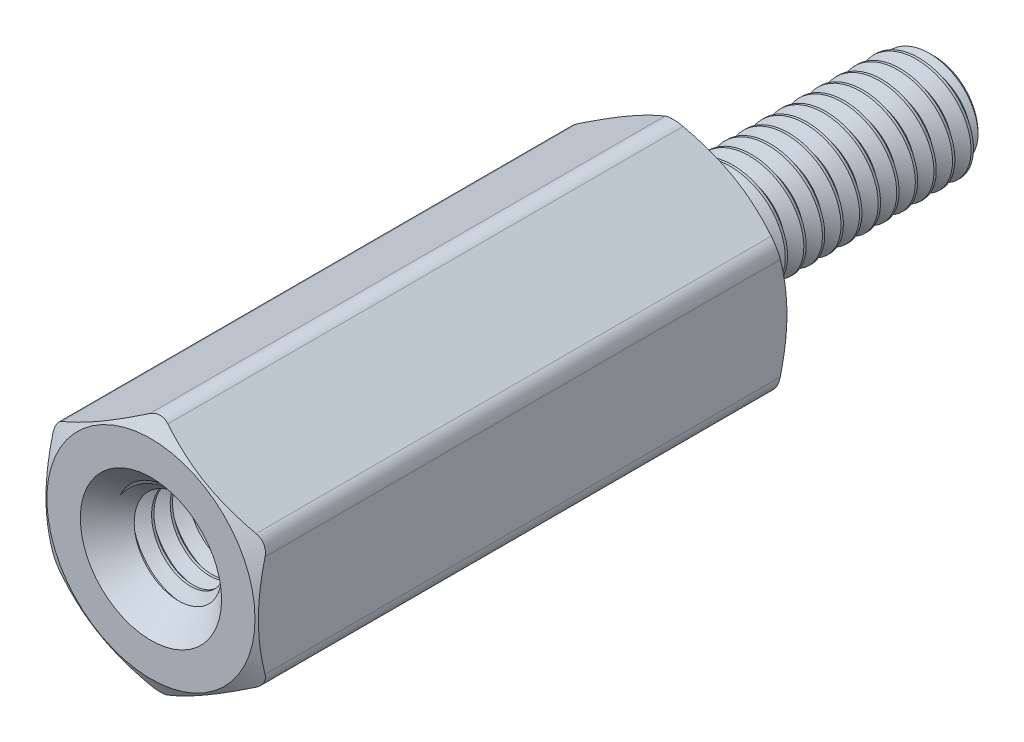
SolidWorks part; units mm, degrees
ref_plane "Front Plane" through (0, 0, 0) normal (0, 0, 1) x (1, 0, 0)
ref_plane "Top Plane" through (0, 0, 0) normal (0, 1, 0) x (1, 0, 0)
ref_plane "Right Plane" through (0, 0, 0) normal (1, 0, 0) x (0, 0, -1)
sketch "Sketch1" plane through (0, 0, 0) normal (0, 0, 1) x (1, 0, 0)
  line L1 (4, 2.3094) -> (0, 4.6188)
  line L2 (0, 4.6188) -> (-4, 2.3094)
  line L3 (-4, 2.3094) -> (-4, -2.3094)
  line L4 (-4, -2.3094) -> (0, -4.6188)
  line L5 (0, -4.6188) -> (4, -2.3094)
  line L6 (4, -2.3094) -> (4, 2.3094)
  circle A0 centre (0, 0) radius 4 construction
  point P10 (0, -4)
  dimension "Hex Size" = 8
sketch "Sketch2" plane through (0, 0, 0) normal (1, 0, 0) x (0, 0, -1)
  line L0 (9.5, 0) -> (-20, 0) construction
  line L2 (0, 2) -> (0, -2) construction
  line L3 (-8.9, 2) -> (-8.9, -2) construction
  line L4 (-20.6563, 2.0758) -> (-20.3063, 1.4696) construction
  line L5 (-20.3063, 1.4696) -> (-19.9563, 2.0758) construction
  line L6 (-19.9563, 2.0758) -> (-20.6563, 2.0758) construction
  line L7 (-20.6125, 2) -> (-20, 2) construction
  line L8 (-20.35, 1.5453) -> (-20.2625, 1.5453) construction
  line L9 (-20.3063, 1.5453) -> (-20.3063, 1.4696) construction
  line L10 (-20.3063, 2) -> (-20.3063, 2.0758) construction
  line L11 (9.4562, 2.0758) -> (10.1562, 2.0758) construction
  line L12 (10.1562, 2.0758) -> (9.8062, 1.4696) construction
  line L13 (9.8062, 1.4696) -> (9.4562, 2.0758) construction
  line L14 (9.5, 2) -> (10.1125, 2) construction
  line L15 (9.7625, 1.5453) -> (9.85, 1.5453) construction
  line L16 (9.8062, 1.5453) -> (9.8062, 1.4696) construction
  line L17 (9.8062, 2) -> (9.8062, 2.0758) construction
  line L18 (0, 4.6188) -> (-20, 4.6188) construction
  point P6 (0, 0)
  point P9 (-8.9, 0)
  dimension "Length" = 20
sketch "Sketch3" plane through (0, 0, 0) normal (1, 0, 0) x (0, 0, -1)
  line L0 (-8.9, 0) -> (9.5, 0)
  line L1 (-8.9, 2) -> (-8.9, -2) construction
  line L2 (9.5, 0) -> (9.5, 1.65)
  line L3 (9.5, 1.65) -> (9.15, 2)
  line L4 (9.15, 2) -> (1.4025, 2)
  line L5 (1.4025, 2) -> (1.14, 1.5453)
  line L6 (-8.9, 0) -> (-8.9, 1.65)
  line L7 (-8.9, 1.65) -> (-9.25, 2)
  line L8 (-9.25, 2) -> (-19.65, 2)
  line L9 (-19.65, 2) -> (-20, 2.35)
  line L10 (9.15, 0) -> (9.15, -2) construction
  line L11 (-20, 2.35) -> (-20, 4)
  line L12 (-20, 4) -> (0, 4)
  line L14 (1.14, 1.5453) -> (0.35, 1.5453)
  line L15 (0, 1.8953) -> (0, 4)
  arc A0 (0, 1.8953) -> (0.35, 1.5453) centre (0.35, 1.8953) ccw
  point P5 (-20, -4)
  point P8 (-18.25, -2)
  point P9 (7.75, -2)
  point P27 (0, 1.5453)
  dimension "D4" = 0.35
  dimension "D2" = 0.35
  dimension "D1" = 45
  dimension "D6" = 1.75
  dimension "D7" = 60
  dimension "D3" = 1.75
  dimension "D5" = 1.14
revolve "Revolve1" add sketch "Sketch3" angle 360 about L0
sketch "Sketch4" plane through (0, 0, 20) normal (0, 0, 1) x (1, 0, 0)
  line L0 (0, 4) -> (0, 2) construction
  line L1 (-4, 2.3094) -> (-4, -2.3094)
  line L2 (-4, -2.3094) -> (0, -4.6188)
  line L3 (0, -4.6188) -> (4, -2.3094)
  line L4 (4, -2.3094) -> (4, 2.3094)
  line L5 (4, 2.3094) -> (0, 4.6188)
  line L6 (0, 4.6188) -> (-4, 2.3094)
  circle A0 centre (0, 0) radius 4 construction
  circle A1 centre (0, 0) radius 3
  circle A2 centre (0, 0) radius 4 construction
  point P16 (0, 3)
extrude "Boss-Extrude1" add sketch "Sketch4" against normal up to surface (20 mm away) up to face at (0, 4, 0)
sketch "Sketch5" plane through (0, 0, 20) normal (0, 0, 1) x (1, 0, 0)
  line L0 (-1.1472, 1.6383) -> (1.1472, -1.6383) construction
  line L1 (0, 2) -> (0, -2) construction
  line L3 (0, -2.7928) -> (0, 2.7928) construction
  circle A0 centre (0, 0) radius 3.92
  point P11 (1.1472, -1.6383)
  dimension "D1" = 7.84
  dimension "D2" = 35
extrude "Cut-Extrude1" cut sketch "Sketch5" against normal through all draft 60 flip side to cut
sketch "Sketch6" plane through (0, 0, 0) normal (0, 0, -1) x (-1, 0, 0)
  circle A0 centre (0, 0) radius 3.92
  circle A1 centre (0, 0) radius 3.92 construction
extrude "Cut-Extrude2" cut sketch "Sketch6" against normal through all draft 60 flip side to cut
fillet "Fillet1" radius 0.68 6 edges at (0, 4.6188, 10) (-4, -2.3094, 10) (0, -4.6188, 10) (4, -2.3094, 10) (4, 2.3094, 10) (-4, 2.3094, 10)
sketch "Drawing1" plane through (0, 0, 0) normal (1, 0, 0) x (0, 0, -1)
  line L0 (-20, 2) -> (-8.9, 2) construction
  line L1 (-8.9, 2) -> (-8.9, -2) construction
  line L2 (-8.9, -2) -> (-20, -2) construction
sketch "Sketch7" plane through (0, 0, 0) normal (-1, 0, 0) x (0, 0, 1)
  line L0 (-9.7625, 1.5453) -> (-9.85, 1.5453)
  line L1 (-9.85, 1.5453) -> (-10.1344, 2.0379)
  line L2 (-10.1562, 2.0758) -> (-9.8062, 1.4696) construction
  line L3 (-10.1344, 2.0379) -> (-9.4781, 2.0379)
  line L4 (-9.8062, 1.4696) -> (-9.4562, 2.0758) construction
  line L5 (-9.4781, 2.0379) -> (-9.7625, 1.5453)
  line L6 (-9.8062, 2) -> (-9.8062, 2.0758) construction
  point P12 (-9.8062, 2.0379)
sketch "Sketch8" plane through (0, 0, -9.5) normal (0, 0, -1) x (-1, 0, 0)
  circle A0 centre (0, 0) radius 2
curve "Helix/Spiral1" pitch 0.7 height 9.215 turns 13.1643
sweep "Cut-Sweep1" cut profiles "Sketch7" path "Helix/Spiral1" align with end faces yes
sketch "Sketch9" plane through (0, 0, 8.9) normal (0, 0, 1) x (1, 0, 0)
  circle A0 centre (0, 0) radius 2.35
extrude "Boss-Extrude2" add sketch "Sketch9" along normal up to surface (11.1 mm away)
sketch "Sketch10" plane through (0, 0, 0) normal (1, 0, 0) x (0, 0, -1)
  line L0 (9.5, 0) -> (-20, 0) construction
  line L1 (-8.9, 2) -> (-20, 2)
  line L2 (-8.9, 2) -> (-8.9, 0)
  line L3 (-8.9, 0) -> (-20, 0)
  line L4 (-20, 2) -> (-20, 0)
revolve "Revolve2" add sketch "Sketch10" angle 360 about L0
sketch "Sketch11" plane through (0, 0, 20) normal (0, 0, 1) x (1, 0, 0)
  circle A0 centre (0, 0) radius 2
  circle A1 centre (0, 0) radius 2 construction
sketch "Sketch12" plane through (0, 0, 0) normal (1, 0, 0) x (0, 0, -1)
  line L0 (-20.35, 1.5453) -> (-20.2625, 1.5453)
  line L1 (-20.2625, 1.5453) -> (-19.9781, 2.0379)
  line L2 (-20.3063, 1.4696) -> (-19.9563, 2.0758) construction
  line L3 (-19.9781, 2.0379) -> (-20.6344, 2.0379)
  line L4 (-20.6563, 2.0758) -> (-20.3063, 1.4696) construction
  line L5 (-20.6344, 2.0379) -> (-20.35, 1.5453)
  line L6 (-20.3063, 2) -> (-20.3063, 2.0758) construction
  point P12 (-20.3063, 2.0379)
curve "Helix/Spiral2" pitch 0.7 height 11.8 turns 16.8571
sweep "Cut-Sweep2" cut profiles "Sketch12" path "Helix/Spiral2" align with end faces yes
combine bodies "Combine1" operation type subtract main body 113 bodies to subtract 114
sketch "Sketch13" plane through (0, 0, 20) normal (0, 0, 1) x (1, 0, 0)
  circle A0 centre (0, 0) radius 2.66
  dimension "D1" = 5.32
extrude "Cut-Extrude3" cut sketch "Sketch13" against normal through all draft 45
equation "\"Thread Pitch (B)/8@Sketch2\" = \"Thread Pitch (B)@Sketch2\" / 8"
equation "\"Thread Pitch (A)/8@Sketch2\" = \"Thread Pitch (A)@Sketch2\" / 8"
equation "\"D1@Sketch5\"=\"Hex Size@Sketch1\" * .98"
equation "\"D1@Fillet1\"=\"Hex Size@Sketch1\" * .085"
equation "\"D2@Sketch3\"=\"Thread Pitch (A)@Sketch2\" * .5"
equation "\"D4@Sketch3\" = \"D2@Sketch3\""
equation "\"D6@Sketch3\" = \"Thread Pitch (A)@Sketch2\" * 2.5"
equation "\"D3@Helix/Spiral1\" = \"Thread Length (A)@Sketch2\" - \"D5@Sketch3\" * .25"
equation "\"D4@Helix/Spiral1\" = \"Thread Pitch (A)@Sketch2\""
equation "\"D3@Sketch3\" = \"Thread Pitch (B)@Sketch2\" * 2.5"
equation "\"D5@Sketch3\" = \"Thread Length (A)@Sketch2\" * .12"
equation "\"D3@Helix/Spiral2\" = \"Minimum Thread Length (B)@Sketch2\" + \"Thread Pitch (B)@Sketch2\""
equation "\"D4@Helix/Spiral2\" = \"Thread Pitch (B)@Sketch2\""
equation "\"D1@Sketch13\"=(\"Hex Size@Sketch1\"-\"Thread Size (A)@Sketch2\")*.33+\"Thread Size (A)@Sketch2\""
